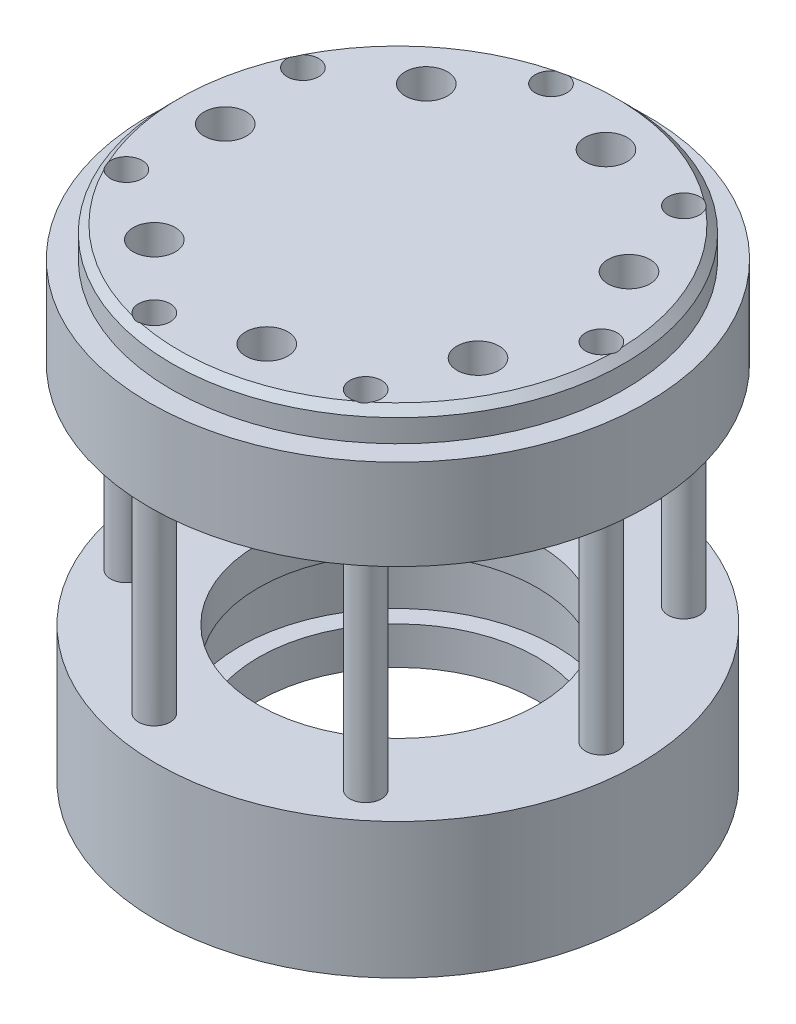
SolidWorks part; units mm, degrees
ref_plane "Front" through (0, 0, 0) normal (0, 0, 1) x (1, 0, 0)
ref_plane "Top" through (0, 0, 0) normal (0, 1, 0) x (1, 0, 0)
ref_plane "Right" through (0, 0, 0) normal (1, 0, 0) x (0, 0, -1)
sketch "Sketch1" plane through (0, 0, 0) normal (0, 1, 0) x (1, 0, 0)
  line L0 (14.55, 0) -> (16, 0) construction
  line L1 (12.45, 0) -> (10.5, 0) construction
  circle A0 centre (0, 0) radius 13.5 construction
  circle A1 centre (13.5, 0) radius 1.05 construction
  circle A2 centre (0, 0) radius 16
  circle A3 centre (0, 0) radius 10.5
  point P9 (12.45, 0)
  dimension "D1" = 2.1
  dimension "D2" = 27
  dimension "D3" = 32
  dimension "D4" = 21
extrude "Boss-Extrude1" add sketch "Sketch1" along normal blind 9
sketch "Sketch2" plane through (0, 9, 0) normal (0, 1, 0) x (1, 0, 0)
  circle A0 centre (0, 0) radius 13.5 construction
  circle A1 centre (13.5, 0) radius 1.05
  circle A2 centre (8.4171, -10.5547) radius 1.05
  circle A3 centre (-3.004, -13.1615) radius 1.05
  circle A4 centre (-12.1631, -5.8574) radius 1.05
  circle A5 centre (-12.1631, 5.8574) radius 1.05
  circle A6 centre (-3.004, 13.1615) radius 1.05
  circle A7 centre (8.4171, 10.5547) radius 1.05
  dimension "D1" = 27
  dimension "D2" = 2.1
  dimension "D3" = 7
extrude "Boss-Extrude2" add sketch "Sketch2" along normal blind 15
sketch "Sketch3" plane through (0, 9, 0) normal (0, 1, 0) x (1, 0, 0)
  circle A0 centre (0, 0) radius 9.25
  circle A1 centre (0, 0) radius 10.5 construction
  circle A2 centre (0, 0) radius 10.5
  dimension "D1" = 18.5
extrude "Boss-Extrude3" add sketch "Sketch3" against normal blind 2.5
extrude "Boss-Extrude4" add sketch "Sketch3<3>" along normal blind 2.5 from surface starting at face at (0, 0, 16)
sketch "Sketch3<3>" plane through (0, 9, 0) normal (0, 1, 0) x (1, 0, 0) same geometry as "Sketch3"
sketch "Sketch4" plane through (0, 24, 0) normal (0, 1, 0) x (1, 0, 0)
  circle A0 centre (0, 0) radius 16.5
  dimension "D1" = 33
extrude "Boss-Extrude5" add sketch "Sketch4" along normal blind 6
sketch "Sketch6" plane through (0, 30, 0) normal (0, 1, 0) x (1, 0, 0)
  circle A0 centre (0, 0) radius 15
  dimension "D1" = 30
extrude "Boss-Extrude6" add sketch "Sketch6" along normal blind 2
sketch "Sketch8" plane through (0, 24, 0) normal (0, -1, 0) x (1, 0, 0)
  circle A0 centre (0, 0) radius 7.5
  dimension "D1" = 15
extrude "Cut-Extrude1" cut sketch "Sketch8" against normal blind 4
chamfer "Chamfer1" distance 0.5 angle 45 1 edges at (0, 24, -7.5)
sketch "Sketch9" plane through (0, 28, 0) normal (0, -1, 0) x (1, 0, 0)
  circle A0 centre (0, 0) radius 6
  dimension "D1" = 12
extrude "Cut-Extrude2" cut sketch "Sketch9" against normal blind 1.5
chamfer "Chamfer2" distance 0.5 angle 45 1 edges at (0, 32, 15)
sketch "Sketch10" plane through (0, 9, 0) normal (0, 1, 0) x (1, 0, 0)
  circle A1 centre (8.4171, -10.5547) radius 1.05
  circle A2 centre (8.4171, -10.5547) radius 1.05
  circle A3 centre (13.5, 0) radius 1.05
  circle A4 centre (13.5, 0) radius 1.05
  circle A7 centre (8.4171, 10.5547) radius 1.05
  circle A8 centre (8.4171, 10.5547) radius 1.05
  circle A9 centre (-3.004, 13.1615) radius 1.05
  circle A10 centre (-3.004, 13.1615) radius 1.05
  circle A11 centre (-12.1631, 5.8574) radius 1.05
  circle A12 centre (-12.1631, 5.8574) radius 1.05
  circle A13 centre (-12.1631, -5.8574) radius 1.05
  circle A14 centre (-12.1631, -5.8574) radius 1.05
  circle A15 centre (-3.004, -13.1615) radius 1.05
  circle A16 centre (-3.004, -13.1615) radius 1.05
  dimension "D1" = 0
  dimension "D2" = 0
  dimension "D4" = 0
  dimension "D5" = 0
  dimension "D6" = 0
  dimension "D7" = 0
  dimension "D8" = 0
extrude "Cut-Extrude3" cut sketch "Sketch10" against normal blind 7
sketch "Sketch11" plane through (0, 24, 0) normal (0, -1, 0) x (1, 0, 0)
  circle A1 centre (8.4171, -10.5547) radius 1.05
  circle A3 centre (8.4171, -10.5547) radius 1.05
  circle A4 centre (-3.004, -13.1615) radius 1.05
  circle A5 centre (-3.004, -13.1615) radius 1.05
  circle A6 centre (-12.1631, -5.8574) radius 1.05
  circle A7 centre (-12.1631, -5.8574) radius 1.05
  circle A8 centre (-12.1631, 5.8574) radius 1.05
  circle A9 centre (-12.1631, 5.8574) radius 1.05
  circle A10 centre (-3.004, 13.1615) radius 1.05
  circle A11 centre (-3.004, 13.1615) radius 1.05
  circle A12 centre (8.4171, 10.5547) radius 1.05
  circle A13 centre (8.4171, 10.5547) radius 1.05
  circle A14 centre (13.5, 0) radius 1.05
  circle A15 centre (13.5, 0) radius 1.05
  dimension "D1" = 0
  dimension "D2" = 0
  dimension "D3" = 0
  dimension "D4" = 0
  dimension "D5" = 0
  dimension "D6" = 0
  dimension "D7" = 0
extrude "Cut-Extrude4" cut sketch "Sketch11" against normal up to surface (8 mm away) up to face at (0, 32, 14.5)
sketch "Sketch12" plane through (0, 24, 0) normal (0, 1, 0) x (1, 0, 0)
  line L0 (0, 0) -> (10.3797, 4.9509) construction
  circle A1 centre (10.3797, 4.9509) radius 3
  circle A2 centre (0, 0) radius 8 construction
  circle A3 centre (0, 0) radius 8 construction
  circle A4 centre (10.3797, 4.9509) radius 1.4 construction
  dimension "D2" = 6
  dimension "D3" = 2.8
  dimension "D1" = 11.5
  dimension "D4" = 25.5
extrude "Cut-Extrude5" cut sketch "Sketch12" along normal blind 5
sketch "Sketch13" plane through (0, 29, 0) normal (0, -1, 0) x (1, 0, 0)
  circle A0 centre (10.3797, -4.9509) radius 1.4
  dimension "D1" = 2.8
extrude "Cut-Extrude6" cut sketch "Sketch13" against normal up to surface (3 mm away) up to face at (0, 32, 0)
pattern_circular "CirPattern1" count 7 over 360 about axis through (0, 30, 0) along (0, 1, 0) of "Cut-Extrude5", "Cut-Extrude6"
chamfer "Chamfer3" distance 0.5 angle 45 7 edges at (-4.2117, 24, -9.6854) (4.9464, 24, -9.3316) (-10.1983, 24, -2.7459) (-8.5054, 24, 6.2613) (-0.4077, 24, 10.5536) (10.3797, 24, -1.9509) (7.9969, 24, 6.8988)
